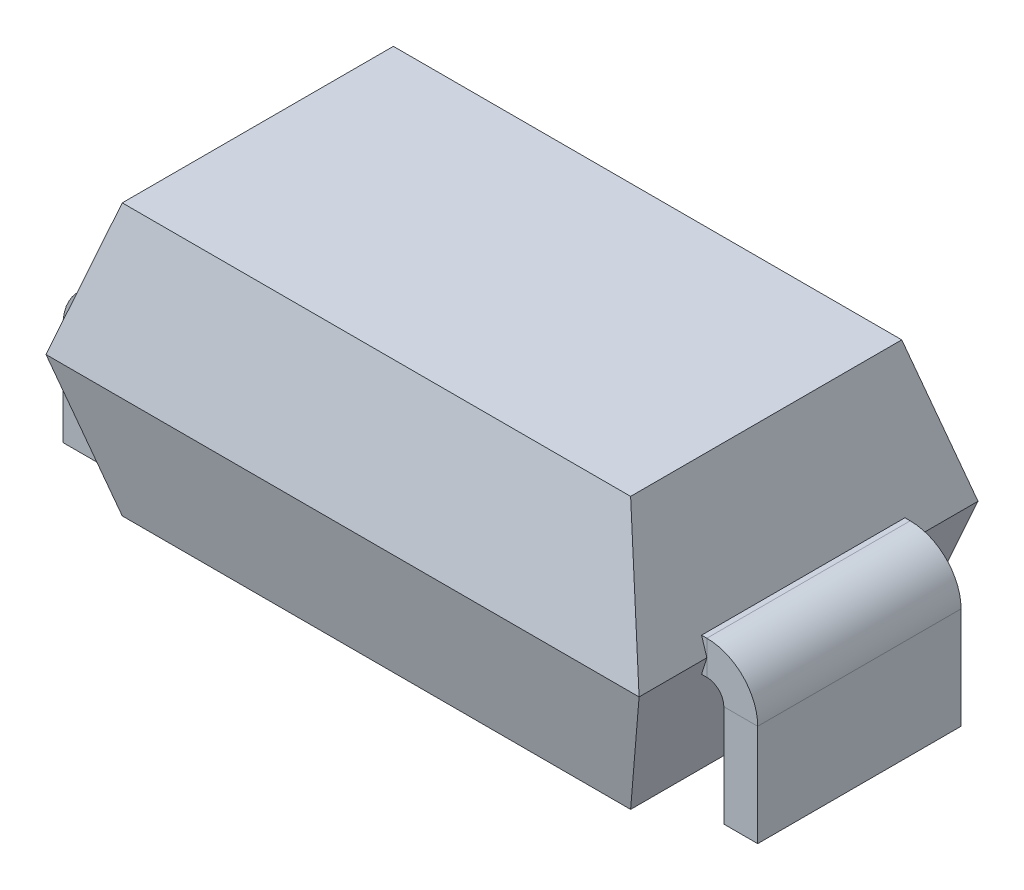
SolidWorks part; units mm, degrees
ref_plane "Front Plane" through (0, 0, 0) normal (0, 0, 1) x (1, 0, 0)
ref_plane "Top Plane" through (0, 0, 0) normal (0, 1, 0) x (1, 0, 0)
ref_plane "Right Plane" through (0, 0, 0) normal (1, 0, 0) x (0, 0, -1)
sketch "Base" plane through (0, 0, 0) normal (0, 1, 0) x (1, 0, 0)
  line L1 (-1.75, 1) -> (1.75, 1)
  line L2 (-1.75, 1) -> (-1.75, -1)
  line L3 (-1.75, -1) -> (1.75, -1)
  line L4 (1.75, 1) -> (1.75, -1)
  line L5 (-1.75, 1) -> (1.75, -1) construction
  line L6 (-1.75, -1) -> (1.75, 1) construction
  point P0 (0, 0)
  dimension "D1" = 2
  dimension "D2" = 3.5
ref_plane "TopRP" through (0, 0.8, 0) normal (0, 1, 0) x (1, 0, 0)
sketch "Top" plane through (0, 0.8, 0) normal (0, 1, 0) x (1, 0, 0)
  line L0 (-1.75, 1) -> (-1.75, -1) construction
  line L1 (-1.5, 0.8) -> (1.5, 0.8)
  line L2 (-1.5, 0.8) -> (-1.5, -0.8)
  line L3 (-1.5, -0.8) -> (1.5, -0.8)
  line L4 (1.5, 0.8) -> (1.5, -0.8)
  line L5 (-1.5, 0.8) -> (1.5, -0.8) construction
  line L6 (-1.5, -0.8) -> (1.5, 0.8) construction
  line L7 (-1.75, 1) -> (1.75, 1) construction
  point P0 (0, 0)
  dimension "D1" = 0.25
  dimension "D2" = 0.2
loft "Loft1" add profiles "Base", "Top" connector at (-1.75, 0, -1) connector at (-1.5, 0.8, -0.8)
mirror "Mirror1" about plane through (0, 0, 0) normal (0, 1, 0) of "Loft1"
sketch "RefP" plane through (0, 0, 0) normal (0, 0, 1) x (1, 0, 0)
  line L0 (-1.75, 0) -> (1.75, 0) construction
  point P0 (1.55, 0)
  point P1 (1.4842, 0)
  dimension "D1" = 0.2
ref_plane "LegP" through (1.55, 0, 0) normal (1, 0, 0) x (0, 0, -1)
sketch "Sketch3" plane through (0, 0, 0) normal (0, 0, 1) x (1, 0, 0)
  line L0 (1.55, 0) -> (1.75, 0)
  line L1 (1.95, -0.2) -> (1.95, -0.8)
  line L2 (1.95, -0.8) -> (1.5, -0.8) construction
  arc A0 (1.75, 0) -> (1.95, -0.2) centre (1.75, -0.2) cw
  point P7 (1.8379, 0)
  point P10 (1.75, 0)
  dimension "D1" = 0.2
sketch "Sketch4" plane through (1.55, 0, 0) normal (1, 0, 0) x (0, 0, -1)
  line L1 (0.6, 0.1) -> (-0.6, 0.1)
  line L2 (0.6, 0.1) -> (0.6, -0.1)
  line L3 (0.6, -0.1) -> (-0.6, -0.1)
  line L4 (-0.6, 0.1) -> (-0.6, -0.1)
  line L5 (0.6, 0.1) -> (-0.6, -0.1) construction
  line L6 (0.6, -0.1) -> (-0.6, 0.1) construction
  point P0 (0, 0)
  dimension "Height" = 0.2
  dimension "Width" = 1.2
sweep "Sweep1" add profiles "Sketch4" path "Sketch3"
mirror "Mirror3" about plane through (0, 0, 0) normal (1, 0, 0) of "Sweep1"
